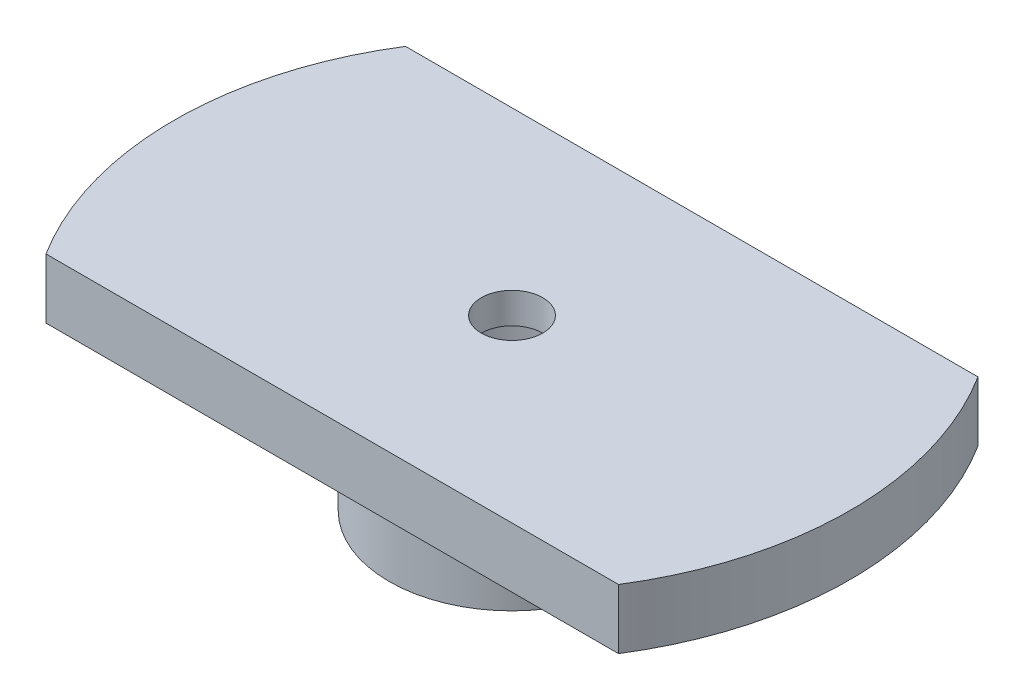
SolidWorks part; units mm, degrees
ref_plane "Front Plane" through (0, 0, 0) normal (0, 0, 1) x (1, 0, 0)
ref_plane "Top Plane" through (0, 0, 0) normal (0, 1, 0) x (1, 0, 0)
ref_plane "Right Plane" through (0, 0, 0) normal (1, 0, 0) x (0, 0, -1)
sketch "Sketch1" plane through (0, 0, 0) normal (0, 1, 0) x (1, 0, 0)
  line L0 (17, 5.85) -> (-17, 5.85)
  line L1 (0, 5.85) -> (0, -5.85) construction
  line L2 (-22.85, 0) -> (22.85, 0) construction
  line L3 (17, -5.85) -> (-17, -5.85)
  arc A0 (-17, 5.85) -> (-22.85, 0) centre (-17, 0) ccw
  arc A1 (-17, -5.85) -> (-22.85, 0) centre (-17, 0) cw
  arc A2 (17, -5.85) -> (22.85, 0) centre (17, 0) ccw
  arc A3 (17, 5.85) -> (22.85, 0) centre (17, 0) cw
  point P4 (0, 0)
  point P7 (-19.2365, 5.85)
  point P16 (-21.9998, 5.85)
  point P17 (23.4877, 0)
  dimension "D1" = 45.7
  dimension "D2" = 11.7
extrude "Boss-Extrude1" add sketch "Sketch1" against normal blind 1.95
sketch "Sketch2" plane through (0, -1.95, 0) normal (0, -1, 0) x (1, 0, 0)
  circle A0 centre (0, 0) radius 4
  dimension "D1" = 8
extrude "Boss-Extrude2" add sketch "Sketch2" along normal blind 3.55
sketch "Sketch3" plane through (0, -5.5, 0) normal (0, -1, 0) x (1, 0, 0)
  circle A0 centre (0, 0) radius 2.86
  dimension "D1" = 5.72
extrude "Cut-Extrude1" cut sketch "Sketch3" against normal blind 4.5
sketch "Sketch4" plane through (0, -1, 0) normal (0, -1, 0) x (1, 0, 0)
  circle A0 centre (0, 0) radius 1
  dimension "D1" = 2
extrude "Cut-Extrude2" cut sketch "Sketch4" against normal up to surface (1 mm away) up to face at (0, 0, 0)
sketch "Sketch5" plane through (0, 0, 0) normal (0, 1, 0) x (1, 0, 0)
  circle A0 centre (0, 0) radius 11
  dimension "D1" = 22
extrude "Cut-Extrude3" cut sketch "Sketch5" against normal through all both and the other way through all flip side to cut
